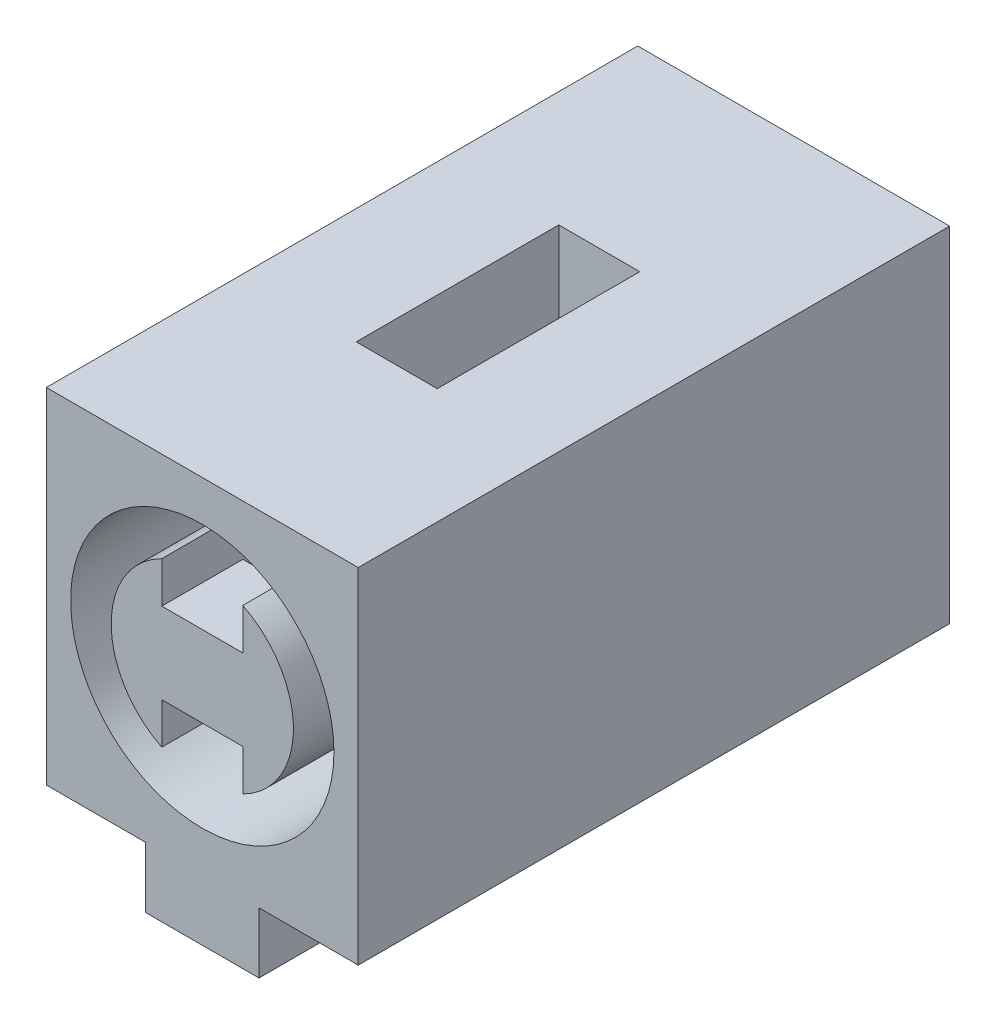
SolidWorks part; units mm, degrees
material "ABS"
ref_plane "Płaszczyzna przednia" through (0, 0, 0) normal (0, 0, 1) x (1, 0, 0)
ref_plane "Płaszczyzna górna" through (0, 0, 0) normal (0, 1, 0) x (1, 0, 0)
ref_plane "Płaszczyzna prawa" through (0, 0, 0) normal (1, 0, 0) x (0, 0, -1)
sketch "Szkic1" plane through (0, 0, 0) normal (0, 1, 0) x (1, 0, 0)
  line L1 (0, 0) -> (7.7, 0)
  line L2 (0, 0) -> (0, 14.6)
  line L3 (0, 14.6) -> (7.7, 14.6)
  line L4 (7.7, 0) -> (7.7, 14.6)
  dimension "D1" = 7.7
  dimension "D2" = 14.6
extrude "Dodanie-wyciągnięcie1" add sketch "Szkic1" along normal blind 8.5
sketch "Szkic2" plane through (0, 0, 0) normal (0, -1, 0) x (1, 0, 0)
  line L0 (7.7, 0) -> (7.7, -14.6) construction
  line L1 (2.85, -9.8) -> (4.85, -9.8)
  line L2 (2.85, -9.8) -> (2.85, -4.8)
  line L3 (2.85, -4.8) -> (4.85, -4.8)
  line L4 (4.85, -9.8) -> (4.85, -4.8)
  line L5 (0, 0) -> (7.7, 0) construction
  point P6 (7.7, -7.3)
  point P7 (4.85, -7.3)
  point P10 (3.85, 0)
  point P11 (3.85, -4.8)
  dimension "D1" = 5
  dimension "D2" = 2
extrude "Wytnij-wyciągnięcie1" cut sketch "Szkic2" against normal blind 10
sketch "Szkic7" plane through (0, 0, 0) normal (0, 0, 1) x (1, 0, 0)
  line L0 (0, 8.5) -> (7.7, 8.5) construction
  line L3 (0, 8.5) -> (0, 0) construction
  circle A0 centre (3.85, 4.25) radius 3.25
  circle A1 centre (3.85, 4.25) radius 2.25
  point P5 (3.85, 8.5)
  point P7 (0, 4.25)
  dimension "D1" = 1
  dimension "D2" = 6.5
extrude "Wytnij-wyciągnięcie4" cut sketch "Szkic7" against normal blind 3.8 contours A0 A1 region at (0.6919, 4.25, 0)
sketch "Szkic10" plane through (0, 0, 0) normal (0, 0, 1) x (1, 0, 0)
  line L0 (0, 8.5) -> (7.7, 8.5) construction
  line L19 (4.85, 7.3423) -> (2.85, 7.3423)
  line L20 (4.85, 7.3423) -> (4.85, 1.1577)
  line L21 (4.85, 1.1577) -> (2.85, 1.1577)
  line L22 (2.85, 7.3423) -> (2.85, 1.1577)
  circle A2 centre (3.85, 4.25) radius 3.25 construction
  point P6 (3.85, 8.5)
  point P13 (3.85, 7.3423)
  dimension "D1" = 2
extrude "Wytnij-wyciągnięcie6" cut sketch "Szkic10" against normal blind 3.8
sketch "Szkic12" plane through (2.85, 0, 0) normal (1, 0, 0) x (0, 0, -1)
  line L0 (0, 2.2344) -> (0, 6.2656) construction
  line L1 (0, 5.25) -> (2, 5.25)
  line L2 (0, 5.25) -> (0, 3.25)
  line L3 (0, 3.25) -> (2, 3.25)
  line L4 (2, 5.25) -> (2, 3.25)
  point P6 (0, 4.25)
  point P7 (0, 4.25)
  dimension "D1" = 2
  dimension "D2" = 2
extrude "Dodanie-wyciągnięcie4" add sketch "Szkic12" along normal blind 2
sketch "Szkic15" plane through (0, 0, 0) normal (0, -1, 0) x (1, 0, 0)
  line L0 (0, 0) -> (7.7, 0) construction
  line L12 (2.45, -4.8) -> (5.25, -4.8)
  line L13 (2.45, -4.8) -> (2.45, 0)
  line L14 (2.45, 0) -> (5.25, 0)
  line L15 (5.25, -4.8) -> (5.25, 0)
  line L17 (4.85, -4.8) -> (2.85, -4.8) construction
  line L18 (0, -7.3) -> (7.7, -7.3) construction
  line L19 (0, -14.6) -> (0, 0) construction
  line L20 (7.7, 0) -> (7.7, -14.6) construction
  line L21 (2.45, -14.6) -> (5.25, -14.6)
  line L22 (5.25, -9.8) -> (5.25, -14.6)
  line L23 (2.45, -9.8) -> (5.25, -9.8)
  line L24 (2.45, -9.8) -> (2.45, -14.6)
  point P7 (3.85, -4.8)
  point P9 (3.85, -4.8)
  dimension "D1" = 2.8
extrude "Dodanie-wyciągnięcie6" add sketch "Szkic15" along normal blind 1.5
